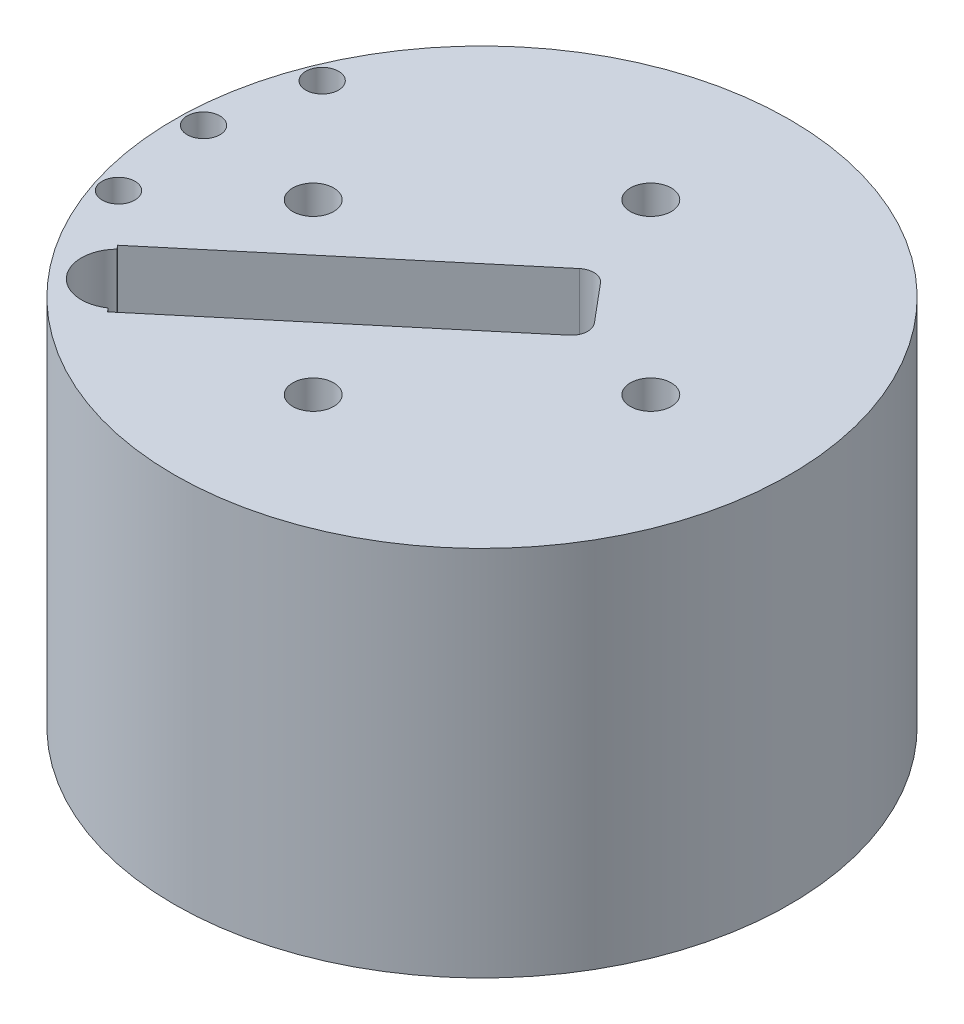
SolidWorks part; units mm, degrees
ref_plane "Front Plane" through (0, 0, 0) normal (0, 0, 1) x (1, 0, 0)
ref_plane "Top Plane" through (0, 0, 0) normal (0, 1, 0) x (1, 0, 0)
ref_plane "Right Plane" through (0, 0, 0) normal (1, 0, 0) x (0, 0, -1)
sketch "Sketch2" plane through (0, 0, 0) normal (0, 1, 0) x (1, 0, 0)
  circle A0 centre (0, 0) radius 47.6885
  dimension "D1" = 95.377
extrude "Boss-Extrude1" add sketch "Sketch2" along normal blind 57.658
sketch "Sketch4" plane through (0, 57.658, 0) normal (0, 1, 0) x (1, 0, 0)
  circle A1 centre (-26.162, 0) radius 3.175
  circle A2 centre (26.162, 0) radius 3.175
  circle A3 centre (0, 26.162) radius 3.175
  circle A4 centre (0, -26.162) radius 3.175
sketch "Sketch5" plane through (0, 57.658, 0) normal (0, 1, 0) x (1, 0, 0)
  line L0 (0, 0) -> (-44.6487, 1.4926)
  line L1 (0, 0) -> (-41.4455, 16.6734)
  line L2 (0, 0) -> (-42.4665, -13.8681)
  line L4 (0, 0) -> (-30.6943, -25.7555)
  circle A1 centre (-41.4455, 16.6734) radius 2.54
  circle A2 centre (0, 0) radius 44.6736
  circle A3 centre (-44.6487, 1.4926) radius 2.54
  circle A4 centre (-42.4665, -13.8681) radius 2.54
  circle A9 centre (-30.6943, -25.7555) radius 5.6388
  dimension "D3" = 11.2776
  dimension "D5" = 89.3472
  dimension "D1" = 20
  dimension "D2" = 20
  dimension "D6" = 21.915
  dimension "D4" = 40.0685
extrude "Cut-Extrude2" cut sketch "Sketch5" against normal through all contours A9 | A1 | A3 | A4
extrude "Cut-Extrude3" cut sketch "Sketch4" against normal through all
sketch "Sketch6" plane through (0, 57.658, 0) normal (0, 1, 0) x (1, 0, 0)
  line L1 (-27.0503, -30.9873) -> (13.8105, 3.299)
  line L2 (-27.0503, -30.9873) -> (-35.2137, -21.2585)
  line L3 (-35.2137, -21.2585) -> (5.6471, 13.0278)
  line L4 (13.8105, 3.299) -> (5.6471, 13.0278)
  dimension "D1" = 53.34
  dimension "D2" = 12.7
  dimension "D3" = 6.35
  dimension "D4" = 12.7
  dimension "D5" = 90
  dimension "D6" = 90
  dimension "D7" = 90
extrude "Cut-Extrude4" cut sketch "Sketch6" against normal blind 25.4
fillet "Fillet2" radius 2.54 5 edges at (-6.6199, 32.258, 13.8441) (-14.7833, 32.258, 4.1154) (9.7288, 32.258, -8.1634) (13.8105, 44.958, -3.299) (5.6471, 44.958, -13.0278)
fillet "Fillet3" radius 2.54 3 edges at (-25.6003, 32.626, 28.1738) (-33.0634, 32.8522, 20.6386) (-26.3747, 32.258, 22.131)
sketch "Sketch11" plane through (0, 0, 0) normal (0, -1, 0) x (1, 0, 0)
  circle A0 centre (0, 26.162) radius 6.35
  circle A1 centre (26.162, 0) radius 6.35
  circle A2 centre (0, -26.162) radius 6.35
  circle A3 centre (-26.162, 0) radius 6.35
  dimension "D1" = 12.7
  dimension "D2" = 12.7
  dimension "D3" = 12.7
  dimension "D4" = 12.7
extrude "Cut-Extrude7" cut sketch "Sketch11" against normal blind 7.62
sketch "Sketch14" plane through (0, 0, 0) normal (0, -1, 0) x (1, 0, 0)
  circle A0 centre (1.0236, -17.4671) radius 2.067
  circle A1 centre (4.5237, 8.9723) radius 2.067
extrude "Cut-Extrude8" cut sketch "Sketch14" against normal blind 19.05
equation "\"D4@Sketch5\"=(3.755/2)-(0.5/2)-0.05"
